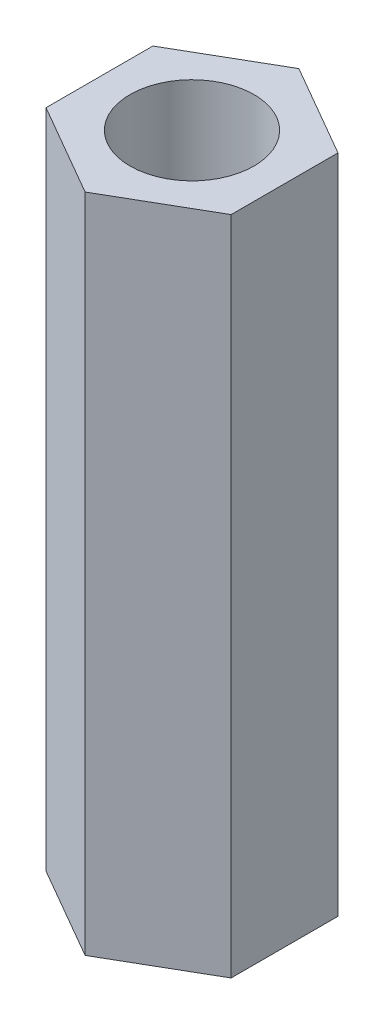
SolidWorks part; units mm, degrees
ref_plane "Front Plane" through (0, 0, 0) normal (0, 0, 1) x (1, 0, 0)
ref_plane "Top Plane" through (0, 0, 0) normal (0, 1, 0) x (1, 0, 0)
ref_plane "Right Plane" through (0, 0, 0) normal (1, 0, 0) x (0, 0, -1)
sketch "Sketch1" plane through (0, 0, 0) normal (0, 1, 0) x (1, 0, 0)
  line L1 (0, -2.0531) -> (1.778, -1.0265)
  line L2 (1.778, -1.0265) -> (1.778, 1.0265)
  line L3 (1.778, 1.0265) -> (0, 2.0531)
  line L4 (0, 2.0531) -> (-1.778, 1.0265)
  line L5 (-1.778, 1.0265) -> (-1.778, -1.0265)
  line L6 (-1.778, -1.0265) -> (0, -2.0531)
  circle A0 centre (0, 0) radius 1.778 construction
  circle A1 centre (0, 0) radius 1.1906
  dimension "D1" = 2.3813
  dimension "D2" = 1.778
extrude "Boss-Extrude1" add sketch "Sketch1" along normal blind 12.7
